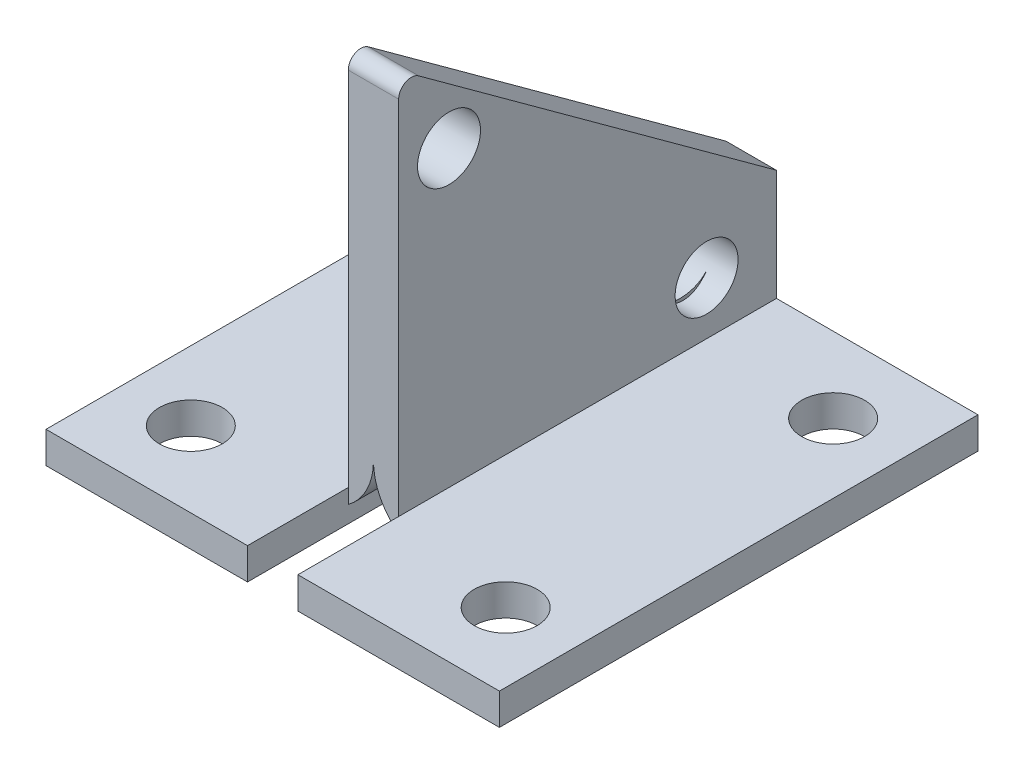
SolidWorks part; units mm, degrees
material "Plain Carbon Steel"
ref_plane "Front Plane" through (0, 0, 0) normal (0, 0, 1) x (1, 0, 0)
ref_plane "Top Plane" through (0, 0, 0) normal (0, 1, 0) x (1, 0, 0)
ref_plane "Right Plane" through (0, 0, 0) normal (1, 0, 0) x (0, 0, -1)
sketch "Sketch1" plane through (0, 0, 0) normal (1, 0, 0) x (0, 0, -1)
  line L30 (-60.9514, 12.5558) -> (-30.9684, -9.2827)
  line L33 (-30.9514, -19.2827) -> (-30.9684, -9.2827)
  line L34 (-30.9514, -19.2827) -> (-60.9514, -19.2827)
  line L36 (-60.9514, -19.2827) -> (-60.9514, 12.5558)
  circle A12 centre (-36.5013, -13.9127) radius 2.5
  circle A13 centre (-56.9514, 5.2129) radius 2.5
  dimension "D6" = 4
  dimension "D4" = 5
  dimension "D5" = 30
  dimension "D3" = 5
  dimension "D1" = 7.3429
  dimension "D7" = 28
  dimension "D2" = 7
  dimension "D8" = 31.8385
  dimension "D9" = 10
extrude "Boss-Extrude2" add sketch "Sketch1" along normal blind 2
sketch "Sketch2" plane through (2, 0, 0) normal (1, 0, 0) x (0, 0, -1)
  line L5 (-68.9514, -20.6093) -> (-68.9514, -19.6093)
  line L7 (-30.9514, -19.2827) -> (-30.9514, -20.6093)
  line L10 (-30.9514, -20.6093) -> (-68.9514, -20.6093)
  line L11 (-68.9514, -19.6093) -> (-68.9514, -18.1093)
  line L14 (-68.9514, -18.1093) -> (-30.9534, -18.1093)
  line L15 (-30.9514, -19.2827) -> (-30.9684, -9.2827) construction
  line L16 (-30.9534, -18.1093) -> (-30.9514, -19.2827)
  point P6 (-65.7002, -18.1093)
  point P10 (-65.7002, -19.2827)
  point P11 (-60.9514, -18.4445)
  dimension "D1" = 38
  dimension "D2" = 2.5
extrude "Boss-Extrude4" add sketch "Sketch2" along normal blind 16
sketch "Sketch3" plane through (0, -18.1093, 0) normal (0, 1, 0) x (1, 0, 0)
  line L0 (18, -30.9534) -> (2, -30.9534) construction
  line L1 (0, -30.9684) -> (0, -60.9514) construction
  circle A0 centre (12.5, -62.9534) radius 2.5
  circle A1 centre (12.5, -36.9534) radius 2.5
  point P8 (0, 0)
  dimension "D1" = 6
  dimension "D2" = 26
  dimension "D3" = 5
  dimension "D5" = 5
  dimension "D6" = 12.5
fillet "Fillet1" radius 5 1 edges at (0, -19.2827, 45.9514)
mirror "Mirror1" about plane through (0, 0, 0) normal (1, 0, 0) of "Boss-Extrude4", "Fillet1", "Boss-Extrude2"
extrude "Cut-Extrude2" cut sketch "Sketch3" against normal through all
mirror "Mirror2" about plane through (0, 0, 0) normal (1, 0, 0) of "Cut-Extrude2"
fillet "Fillet2" radius 1 1 edges at (0, 12.5558, 60.9514)
